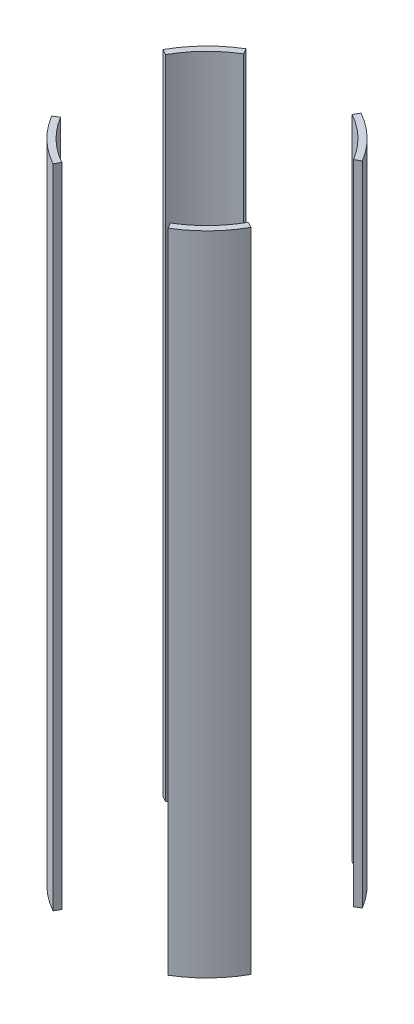
SolidWorks part; units mm, degrees
ref_plane "Front Plane" through (0, 0, 0) normal (0, 0, 1) x (1, 0, 0)
ref_plane "Top Plane" through (0, 0, 0) normal (0, 1, 0) x (1, 0, 0)
ref_plane "Right Plane" through (0, 0, 0) normal (1, 0, 0) x (0, 0, -1)
sketch "Sketch2" plane through (0, 0, 0) normal (0, 1, 0) x (1, 0, 0)
  circle A0 centre (0, 0) radius 88.9
  circle A1 centre (0, 0) radius 83.82
  dimension "D1" = 177.8
  dimension "D2" = 167.64
extrude "Boss-Extrude1" add sketch "Sketch2" along normal mid plane 508
sketch "Sketch3" plane through (0, 0, 0) normal (0, 1, 0) x (1, 0, 0)
  line L0 (0, 0) -> (169.6618, 101.6776)
  line L1 (-58.1167, 96.9749) -> (0, 0)
  line L2 (0, 0) -> (53.9, 96.9749)
  line L3 (53.9, 96.9749) -> (-58.1167, 96.9749)
  line L4 (0, 0) -> (70.9917, -118.4586)
  line L5 (70.9917, -118.4586) -> (-65.8409, -118.4586)
  line L6 (-65.8409, -118.4586) -> (0, 0)
  line L7 (169.6618, 101.6776) -> (169.6618, -94.3004)
  line L8 (169.6618, -94.3004) -> (0, 0)
  line L9 (0, 0) -> (-123.7413, 68.7771)
  line L10 (-123.7413, 68.7771) -> (-123.7413, -74.1577)
  line L11 (-123.7413, -74.1577) -> (0, 0)
  dimension "D1" = 60
  dimension "D2" = 60
  dimension "D3" = 60
  dimension "D4" = 60
  dimension "D5" = 30
  dimension "D6" = 30
extrude "Cut-Extrude1" cut sketch "Sketch3" against normal through all both and the other way through all contours L8 L7 L0 | L2 L3 L1 | L10 L11 L9 | L6 L5 L4 region at (-1.4056, 0, -64.65) region at (1.7169, 0, 78.9724) region at (113.1078, 0, -2.4591) region at (-82.4942, 0, 1.7935)
equation "\"D1@Boss-Extrude1\"=3*12"
